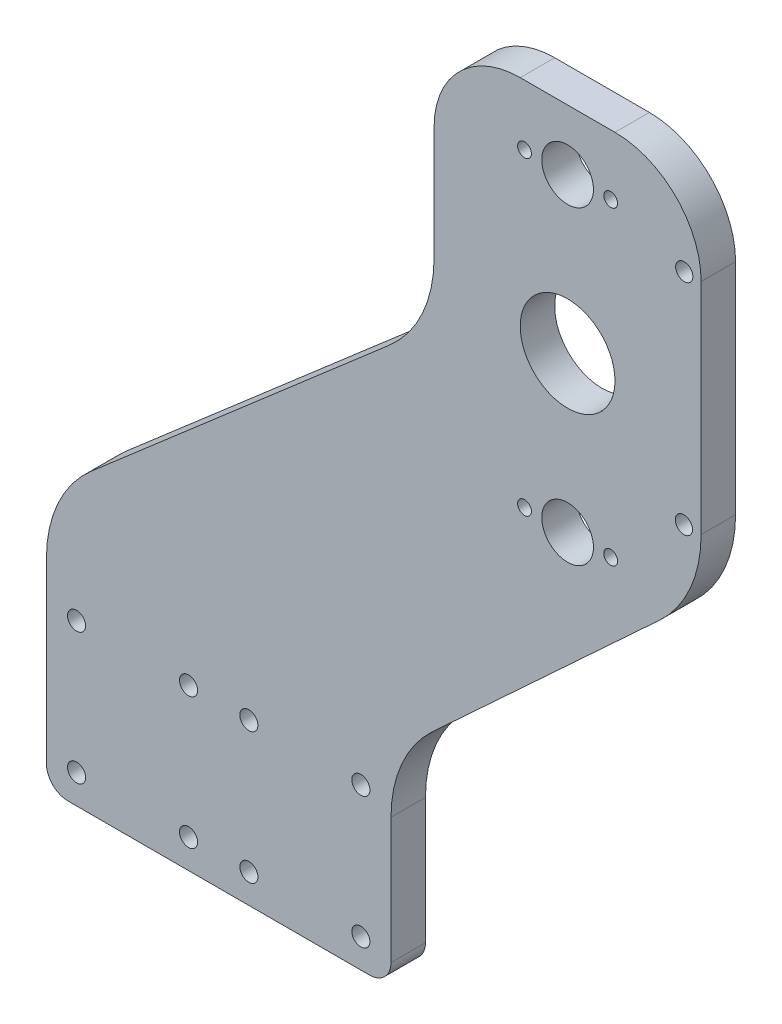
SolidWorks part; units mm, degrees
ref_plane "Front Plane" through (0, 0, 0) normal (0, 0, 1) x (1, 0, 0)
ref_plane "Top Plane" through (0, 0, 0) normal (0, 1, 0) x (1, 0, 0)
ref_plane "Right Plane" through (0, 0, 0) normal (1, 0, 0) x (0, 0, -1)
sketch "Sketch1" plane through (0, 0, 0) normal (0, 0, 1) x (1, 0, 0)
  line L0 (-23.7069, -89.4353) -> (-23.7069, -15.4242) construction
  line L1 (-58.7069, -89.4353) -> (11.2931, -89.4353)
  line L2 (-63.7069, -84.4353) -> (-63.7069, -43.1405)
  line L3 (-63.7069, -84.4353) -> (-23.7069, -84.4353) construction
  line L4 (16.2931, -84.4353) -> (16.2931, -55.2061)
  line L5 (46.2931, 108.5094) -> (68.2931, 108.5094)
  line L6 (26.2931, 88.5094) -> (26.2931, 62.2146)
  line L7 (57.2931, 108.5094) -> (57.2931, 22.5694) construction
  line L8 (88.2931, 88.5094) -> (88.2931, 37.6266)
  line L9 (-43.7069, -67.4353) -> (-43.7069, -84.4353) construction
  line L10 (-56.7069, -52.1853) -> (-30.7069, -52.1853) construction
  line L11 (15.933, 39.537) -> (-53.3469, -20.463)
  line L12 (78.6643, 15.6036) -> (25.9218, -33.1831)
  line L13 (-56.7069, -52.1853) -> (-56.7069, -82.6853) construction
  line L14 (-56.7069, -82.6853) -> (-30.7069, -82.6853) construction
  line L15 (-30.7069, -52.1853) -> (-30.7069, -82.6853) construction
  line L16 (-56.7069, -52.1853) -> (-30.7069, -82.6853) construction
  line L17 (-56.7069, -82.6853) -> (-30.7069, -52.1853) construction
  line L18 (57.2931, 94.5094) -> (57.2931, 22.5694) construction
  arc A0 (78.6643, 15.6036) -> (88.2931, 37.6266) centre (58.2931, 37.6266) ccw
  arc A1 (15.933, 39.537) -> (26.2931, 62.2146) centre (-3.7069, 62.2146) ccw
  arc A2 (16.2931, -55.2061) -> (25.9218, -33.1831) centre (46.2931, -55.2061) cw
  arc A3 (-63.7069, -43.1405) -> (-53.3469, -20.463) centre (-33.7069, -43.1405) cw
  arc A4 (88.2931, 88.5094) -> (68.2931, 108.5094) centre (68.2931, 88.5094) ccw
  arc A5 (46.2931, 108.5094) -> (26.2931, 88.5094) centre (46.2931, 88.5094) ccw
  arc A6 (16.2931, -84.4353) -> (11.2931, -89.4353) centre (11.2931, -84.4353) cw
  arc A7 (-58.7069, -89.4353) -> (-63.7069, -84.4353) centre (-58.7069, -84.4353) cw
  circle A8 centre (-56.7069, -52.1853) radius 2.1
  circle A9 centre (-30.7069, -52.1853) radius 2.1
  circle A10 centre (-30.7069, -82.6853) radius 2.1
  circle A11 centre (-56.7069, -82.6853) radius 2.1
  circle A12 centre (9.2931, -82.6853) radius 2.1
  circle A13 centre (-16.7069, -82.6853) radius 2.1
  circle A14 centre (-16.7069, -52.1853) radius 2.1
  circle A15 centre (9.2931, -52.1853) radius 2.1
  circle A16 centre (57.2931, 94.5094) radius 6
  circle A17 centre (57.2931, 22.5694) radius 6
  circle A18 centre (57.2931, 58.5394) radius 11
  circle A19 centre (84.2931, 37.6266) radius 2
  circle A20 centre (84.3759, 88.5283) radius 2
  circle A21 centre (47.2931, 94.5094) radius 1.6
  circle A22 centre (47.2931, 22.5694) radius 1.6
  circle A23 centre (67.2931, 94.5094) radius 1.6
  circle A24 centre (67.2931, 22.5694) radius 1.6
  point P0 (0, 0)
  point P1 (57.2931, 82.2289)
  point P15 (26.2931, 48.5094)
  point P20 (-63.7069, -29.4353)
  point P23 (88.2931, 108.5094)
  point P26 (26.2931, 108.5094)
  point P29 (16.2931, -89.4353)
  point P32 (-63.7069, -89.4353)
  point P35 (-43.7069, -67.4353)
  dimension "D5" = 30
  dimension "D6" = 20
  dimension "D7" = 5
  dimension "D14" = 71.94
  dimension "D12" = 4
  dimension "D16" = 10
  dimension "D17" = 10
  dimension "D1" = 80
  dimension "D2" = 22
  dimension "D3" = 90
  dimension "D4" = 60
  dimension "D8" = 26
  dimension "D9" = 60
  dimension "D10" = 22
  dimension "D11" = 60
  dimension "D13" = 30.5
  dimension "D15" = 14
extrude "Boss-Extrude1" add sketch "Sketch1" along normal blind 8
